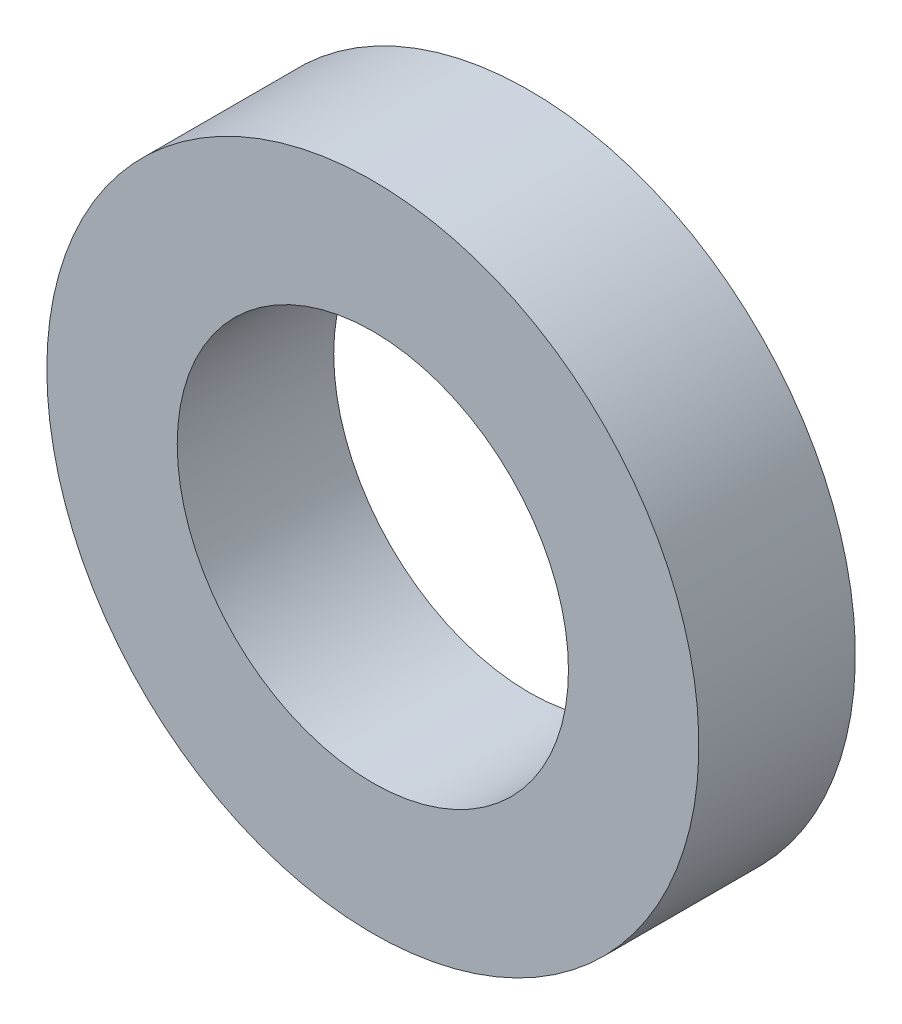
SolidWorks part; units mm, degrees
ref_plane "Front Plane" through (0, 0, 0) normal (0, 0, 1) x (1, 0, 0)
ref_plane "Top Plane" through (0, 0, 0) normal (0, 1, 0) x (1, 0, 0)
ref_plane "Right Plane" through (0, 0, 0) normal (1, 0, 0) x (0, 0, -1)
sketch "Sketch1" plane through (0, 0, 0) normal (0, 0, 1) x (1, 0, 0)
  circle A0 centre (0, 0) radius 15.875
  circle A1 centre (0, 0) radius 9.525
  dimension "D1" = 31.75
  dimension "D2" = 19.05
extrude "Boss-Extrude1" add sketch "Sketch1" along normal blind 7.62
